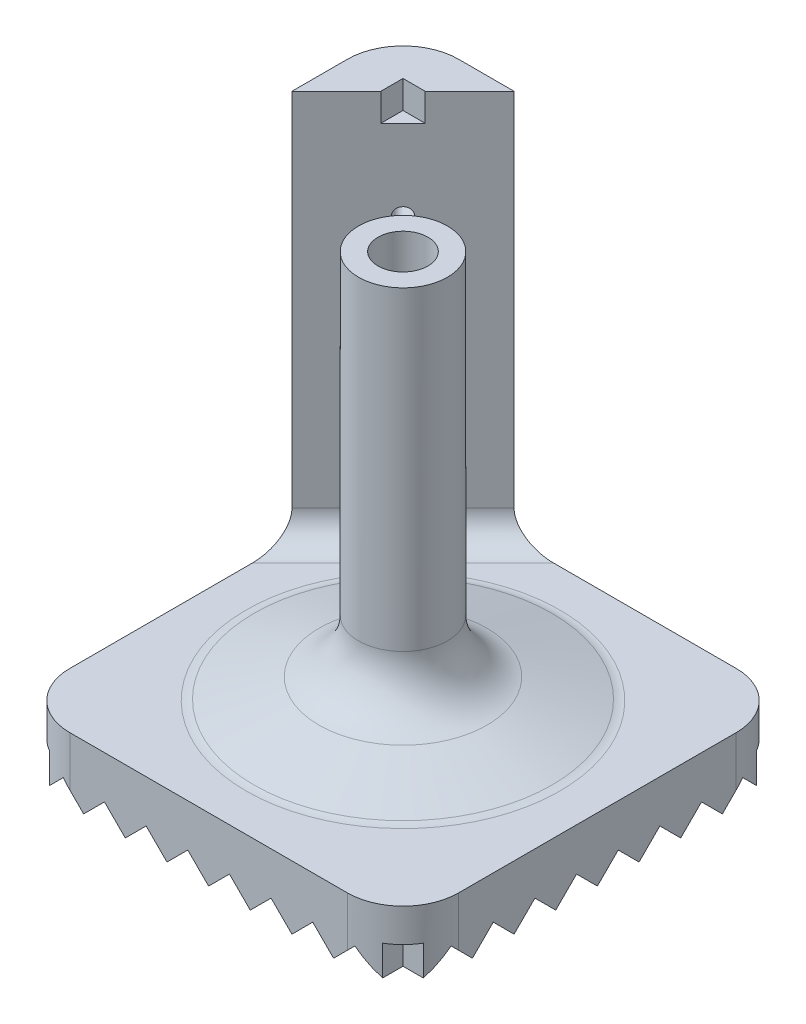
SolidWorks part; units mm, degrees
ref_plane "前视基准面" through (0, 0, 0) normal (0, 0, 1) x (1, 0, 0)
ref_plane "上视基准面" through (0, 0, 0) normal (0, 1, 0) x (1, 0, 0)
ref_plane "右视基准面" through (0, 0, 0) normal (1, 0, 0) x (0, 0, -1)
sketch "草图1" plane through (0, 0, 0) normal (0, 1, 0) x (1, 0, 0)
  line L1 (-35, 35) -> (35, 35)
  line L2 (-35, 35) -> (-35, -35)
  line L3 (-35, -35) -> (35, -35)
  line L4 (35, 35) -> (35, -35)
  line L5 (-35, 35) -> (35, -35) construction
  line L6 (-35, -35) -> (35, 35) construction
  point P0 (0, 0)
  dimension "D1" = 70
  dimension "D2" = 70
extrude "凸台-拉伸1" add sketch "草图1" along normal blind 6
sketch "草图2" plane through (0, 6, 0) normal (0, 1, 0) x (1, 0, 0)
  circle A0 centre (0, 0) radius 8
  dimension "D1" = 16
extrude "凸台-拉伸2" add sketch "草图2" along normal blind 70
sketch "草图3" plane through (0, 0, 0) normal (0, 1, 0) x (1, 0, 0)
  circle A0 centre (0, 0) radius 4.5
  dimension "D1" = 9
extrude "切除-拉伸3" cut sketch "草图3" along normal through all
sketch "草图4" plane through (0, 6, 0) normal (0, 1, 0) x (1, 0, 0)
  line L0 (-35, 35) -> (-15, 35)
  line L1 (35, 35) -> (-35, 35) construction
  line L2 (-15, 35) -> (-35, 15)
  line L3 (-35, 35) -> (-35, -35) construction
  line L4 (-35, 15) -> (-35, 35)
  dimension "D1" = 20
  dimension "D2" = 20
extrude "凸台-拉伸3" add sketch "草图4" along normal blind 70
sketch "草图5" plane through (-25, 0, -25) normal (0.7071, 0, 0.7071) x (0.7071, 0, -0.7071)
  circle A0 centre (0, 45) radius 2.5
  circle A1 centre (0, 56.503) radius 1.5
  dimension "D1" = 5
  dimension "D2" = 3
fillet "圆角1" radius 10 4 edges at (-35, 3, 35) (35, 3, 35) (35, 3, -35) (-35, 38, -35)
extrude "切除-拉伸5" cut sketch "草图5" against normal through all
sketch "草图7" plane through (0, 76, 0) normal (0, 1, 0) x (1, 0, 0)
  line L0 (-23, 27) -> (-27, 27)
  line L1 (-35, 15) -> (-15, 35) construction
  line L2 (-27, 27) -> (-27, 23)
  line L3 (-27, 23) -> (-23, 27)
  line L4 (-35, 15) -> (-15, 35) construction
  point P5 (-25, 25)
  point P8 (-25, 25)
  dimension "D1" = 4
  dimension "D2" = 0
extrude "切除-拉伸6" cut sketch "草图7" against normal blind 5
sketch "草图8" plane through (0, 0, -35) normal (0, 0, -1) x (-1, 0, 0)
  line L1 (-22.5, -5.437) -> (-18.75, -1.687)
  line L2 (-30, 0) -> (-30, -5.437)
  line L3 (-18.75, -1.687) -> (-15, -5.437)
  line L4 (-15, -5.437) -> (-11.25, -1.687)
  line L5 (-11.25, -1.687) -> (-7.5, -5.437)
  line L6 (-7.5, -5.437) -> (-3.75, -1.687)
  line L7 (-35, 0) -> (-25, 0) construction
  line L8 (-3.75, -1.687) -> (0, -5.437)
  line L9 (0, -5.437) -> (3.75, -1.687)
  line L10 (3.75, -1.687) -> (7.5, -5.437)
  line L11 (7.5, -5.437) -> (11.25, -1.687)
  line L12 (11.25, -1.687) -> (15, -5.437)
  line L13 (15, -5.437) -> (18.75, -1.687)
  line L14 (-30, -5.437) -> (-26.25, -1.687)
  line L15 (18.75, -1.687) -> (22.5, -5.437)
  line L17 (30, 0) -> (-30, 0)
  line L18 (-26.25, -1.687) -> (-22.5, -5.437)
  line L19 (30, 0) -> (30, -5.437)
  line L20 (30, -5.437) -> (26.25, -1.687)
  line L21 (26.25, -1.687) -> (22.5, -5.437)
  line L23 (-25, 6) -> (-25, 0) construction
  line L24 (25, 0) -> (25, 76) construction
  dimension "D1" = 5
  dimension "D2" = 45
  dimension "D3" = 5
extrude "凸台-拉伸4" add sketch "草图8" against normal up to surface (70 mm away) up to face at (0, 3, 35)
sketch "草图9" plane through (-35, 0, 0) normal (-1, 0, 0) x (0, 0, 1)
  line L0 (-22.5, -5.437) -> (-18.75, -1.687)
  line L1 (-30, 0) -> (-30, -5.437)
  line L2 (-18.75, -1.687) -> (-15, -5.437)
  line L3 (-15, -5.437) -> (-11.25, -1.687)
  line L4 (-11.25, -1.687) -> (-7.5, -5.437)
  line L5 (-7.5, -5.437) -> (-3.75, -1.687)
  line L6 (-3.75, -1.687) -> (0, -5.437)
  line L7 (0, -5.437) -> (3.75, -1.687)
  line L8 (3.75, -1.687) -> (7.5, -5.437)
  line L9 (7.5, -5.437) -> (11.25, -1.687)
  line L10 (11.25, -1.687) -> (15, -5.437)
  line L11 (15, -5.437) -> (18.75, -1.687)
  line L12 (-30, -5.437) -> (-26.25, -1.687)
  line L13 (18.75, -1.687) -> (22.5, -5.437)
  line L14 (30, 0) -> (-30, 0)
  line L15 (-26.25, -1.687) -> (-22.5, -5.437)
  line L16 (30, 0) -> (30, -5.437)
  line L17 (30, -5.437) -> (26.25, -1.687)
  line L18 (26.25, -1.687) -> (22.5, -5.437)
  line L19 (-25, 76) -> (-25, 0) construction
  line L20 (25, 0) -> (25, 6) construction
  line L21 (-25, 0) -> (25, 0) construction
  line L22 (35, -5.437) -> (-35, -5.437) construction
  dimension "D1" = 5
  dimension "D2" = 5
  dimension "D3" = 45
extrude "凸台-拉伸5" add sketch "草图9" against normal up to surface (70 mm away) up to face at (35, 3, 0)
sketch "草图10" plane through (-35, 0, 0) normal (-1, 0, 0) x (0, 0, 1)
  line L0 (-22.5, -5.437) -> (-18.75, -1.687)
  line L2 (-18.75, -1.687) -> (-15, -5.437)
  line L3 (-15, -5.437) -> (-11.25, -1.687)
  line L4 (-11.25, -1.687) -> (-7.5, -5.437)
  line L5 (-7.5, -5.437) -> (-3.75, -1.687)
  line L6 (-3.75, -1.687) -> (0, -5.437)
  line L7 (0, -5.437) -> (3.75, -1.687)
  line L8 (3.75, -1.687) -> (7.5, -5.437)
  line L9 (7.5, -5.437) -> (11.25, -1.687)
  line L10 (11.25, -1.687) -> (15, -5.437)
  line L11 (15, -5.437) -> (18.75, -1.687)
  line L12 (-30, -5.437) -> (-26.25, -1.687)
  line L13 (18.75, -1.687) -> (22.5, -5.437)
  line L15 (-26.25, -1.687) -> (-22.5, -5.437)
  line L17 (30, -5.437) -> (26.25, -1.687)
  line L18 (26.25, -1.687) -> (22.5, -5.437)
  line L19 (-30, -5.437) -> (30, -5.437)
  line L20 (-30, -5.437) -> (-35, -5.437) construction
  line M24 (-30, -5.437) -> (-26.25, -1.687)
  line M25 (-26.25, -1.687) -> (-22.5, -5.437)
  line M26 (-22.5, -5.437) -> (-18.75, -1.687)
  line M27 (-18.75, -1.687) -> (-15, -5.437)
  line M28 (-15, -5.437) -> (-11.25, -1.687)
  line M29 (-11.25, -1.687) -> (-7.5, -5.437)
  line M30 (-7.5, -5.437) -> (-3.75, -1.687)
  line M31 (-3.75, -1.687) -> (0, -5.437)
  line M32 (0, -5.437) -> (3.75, -1.687)
  line M33 (3.75, -1.687) -> (7.5, -5.437)
  line M34 (7.5, -5.437) -> (11.25, -1.687)
  line M35 (11.25, -1.687) -> (15, -5.437)
  line M36 (15, -5.437) -> (18.75, -1.687)
  line M37 (18.75, -1.687) -> (22.5, -5.437)
  line M38 (22.5, -5.437) -> (26.25, -1.687)
  line M39 (26.25, -1.687) -> (30, -5.437)
  dimension "D1" = 45
extrude "切除-拉伸7" cut sketch "草图10" against normal up to surface (70 mm away) contours L19 M24 M25 | L19 M26 M27 | L19 M28 M29 | L19 M30 M31 | L19 M32 M33 | L19 M34 M35 | L19 M36 M37 | L19 M38 M39 region at (-35, -4.187, 26.25) region at (-35, -4.187, 18.75) region at (-35, -4.187, 11.25) region at (-35, -4.187, 3.75) region at (-35, -4.187, -3.75) region at (-35, -4.187, -11.25) region at (-35, -4.187, -26.25) region at (-35, -4.187, -18.75) up to face at (35, -2.1926, 0)
sketch "草图11" plane through (0, 0, 35) normal (0, 0, 1) x (1, 0, 0)
  line L0 (-22.5, -5.437) -> (-18.75, -1.687)
  line L2 (-18.75, -1.687) -> (-15, -5.437)
  line L3 (-15, -5.437) -> (-11.25, -1.687)
  line L4 (-11.25, -1.687) -> (-7.5, -5.437)
  line L5 (-7.5, -5.437) -> (-3.75, -1.687)
  line L6 (-3.75, -1.687) -> (0, -5.437)
  line L7 (0, -5.437) -> (3.75, -1.687)
  line L8 (3.75, -1.687) -> (7.5, -5.437)
  line L9 (7.5, -5.437) -> (11.25, -1.687)
  line L10 (11.25, -1.687) -> (15, -5.437)
  line L11 (15, -5.437) -> (18.75, -1.687)
  line L12 (-30, -5.437) -> (-26.25, -1.687)
  line L13 (18.75, -1.687) -> (22.5, -5.437)
  line L15 (-26.25, -1.687) -> (-22.5, -5.437)
  line L17 (30, -5.437) -> (26.25, -1.687)
  line L18 (26.25, -1.687) -> (22.5, -5.437)
  line L19 (-30, -5.437) -> (30, -5.437)
  line L21 (-30, -5.437) -> (-26.25, -1.687) construction
  line L22 (-30, 0) -> (-30, -5.437) construction
  line L23 (26.25, -1.687) -> (30, -5.437) construction
  line L24 (30, -5.437) -> (30, 0) construction
  line M51 (-30, -5.437) -> (-26.25, -1.687)
  line M52 (-26.25, -1.687) -> (-22.5, -5.437)
  line M53 (-22.5, -5.437) -> (-18.75, -1.687)
  line M54 (-18.75, -1.687) -> (-15, -5.437)
  line M55 (-15, -5.437) -> (-11.25, -1.687)
  line M56 (-11.25, -1.687) -> (-7.5, -5.437)
  line M57 (-7.5, -5.437) -> (-3.75, -1.687)
  line M58 (-3.75, -1.687) -> (0, -5.437)
  line M59 (0, -5.437) -> (3.75, -1.687)
  line M60 (3.75, -1.687) -> (7.5, -5.437)
  line M61 (7.5, -5.437) -> (11.25, -1.687)
  line M62 (11.25, -1.687) -> (15, -5.437)
  line M63 (15, -5.437) -> (18.75, -1.687)
  line M64 (18.75, -1.687) -> (22.5, -5.437)
  line M65 (22.5, -5.437) -> (26.25, -1.687)
  line M66 (26.25, -1.687) -> (30, -5.437)
  dimension "D1" = 45
extrude "切除-拉伸8" cut sketch "草图11" against normal up to surface (70 mm away) contours L19 M65 M66 | L19 M63 M64 | L19 M61 M62 | L19 M59 M60 | L19 M57 M58 | L19 M55 M56 | L19 M53 M54 | L19 M51 M52 region at (26.25, -4.187, 35) region at (18.75, -4.187, 35) region at (11.25, -4.187, 35) region at (3.75, -4.187, 35) region at (-3.75, -4.187, 35) region at (-11.25, -4.187, 35) region at (-26.25, -4.187, 35) region at (-18.75, -4.187, 35) up to face at (-1.2, 4.0628, -35)
sketch "草图12" plane through (0, 6, 0) normal (0, 1, 0) x (1, 0, 0)
  line L0 (-25, 35) -> (-35, 35)
  line L1 (-35, 35) -> (-35, 25)
  line L2 (25, 35) -> (35, 35)
  line L3 (35, 35) -> (35, 25)
  line L4 (35, -25) -> (35, -35)
  line L5 (35, -35) -> (25, -35)
  line L6 (-25, -35) -> (-35, -35)
  line L7 (-35, -35) -> (-35, -25)
  line L8 (-25, -35) -> (25, -35) construction
  line L9 (35, -25) -> (35, 25) construction
  arc A0 (-35, -25) -> (-25, -35) centre (-25, -25) ccw
  arc A1 (25, -35) -> (35, -25) centre (25, -25) ccw
  arc A2 (35, 25) -> (25, 35) centre (25, 25) ccw
  arc A3 (35, 25) -> (25, 35) centre (25, 25) ccw construction
  arc A4 (-25, 35) -> (-35, 25) centre (-25, 25) ccw
  arc A5 (-25, 35) -> (-35, 25) centre (-25, 25) ccw construction
  arc M5 (-35, -25) -> (-25, -35) centre (-25, -25) ccw
  arc M7 (25, -35) -> (35, -25) centre (25, -25) ccw
  arc M9 (35, 25) -> (25, 35) centre (25, 25) ccw
extrude "切除-拉伸9" cut sketch "草图12" against normal blind 16 contours A4 L0 L1 | L3 L2 M9 | L5 L4 M7 | L7 L6 M5 region at (-32.7663, 6, -32.7663) region at (32.7663, 6, -32.7663) region at (32.7663, 6, 32.7663) region at (-32.7663, 6, 32.7663)
sketch "草图13" plane through (0, 76, 0) normal (0, 1, 0) x (1, 0, 0)
  circle A0 centre (0, 0) radius 4.5
extrude "切除-拉伸10" cut sketch "草图13" against normal through all both and the other way through all
ref_plane "基准面1" through (0, 0, 0) normal (-0.7071, 0, 0.7071) x (0.7071, 0, 0.7071)
sketch "草图15" plane through (0, 0, 0) normal (-0.7071, 0, 0.7071) x (0.7071, 0, 0.7071)
  line L0 (-35.3553, 19.6803) -> (-32.8796, 6)
  line L1 (-35.3553, 76) -> (-35.3553, 6) construction
  line L2 (-35.3553, 6) -> (-7.0711, 6) construction
  line L3 (-32.8796, 6) -> (-35.3553, 6)
  line L4 (-35.3553, 6) -> (-35.3553, 19.6803)
ref_axis "基准轴1" through (0, 339.9566, 0) along (0, -1, 0)
sketch "草图17" plane through (0, 0, 0) normal (-0.7071, 0, 0.7071) x (0.7071, 0, 0.7071)
  line L0 (8, 11.8562) -> (27.505, 6)
  line L1 (8, 6) -> (8, 76) construction
  line L2 (7.0711, 6) -> (42.4264, 6) construction
  line L3 (27.505, 6) -> (8, 6)
  line L4 (8, 6) -> (8, 76) construction
  line L5 (8, 6) -> (8, 11.8562)
revolve "旋转1" add sketch "草图17" angle 360 about axis through (0, 339.9566, 0) along (0, -1, 0)
sketch "草图18" plane through (0, 0, 0) normal (-0.7071, 0, 0.7071) x (0.7071, 0, 0.7071)
  line L0 (8, 11.8562) -> (8, 76) construction
  line L1 (27.505, 6) -> (8, 11.8562) construction
  line L2 (8, 25.0277) -> (8, 11.8562)
  line L3 (8, 11.8562) -> (12.5528, 10.4892)
  spline S0 degree 1 poles (8, 25.0277) (12.5528, 10.4892) knots 0 0 1 1
fillet "圆角2" radius 10 1 edges at (0, 11.8562, -8)
fillet "圆角3" radius 5 1 edges at (0, 6, 27.505)
fillet "圆角5" radius 5 1 edges at (-25, 6, -25)
